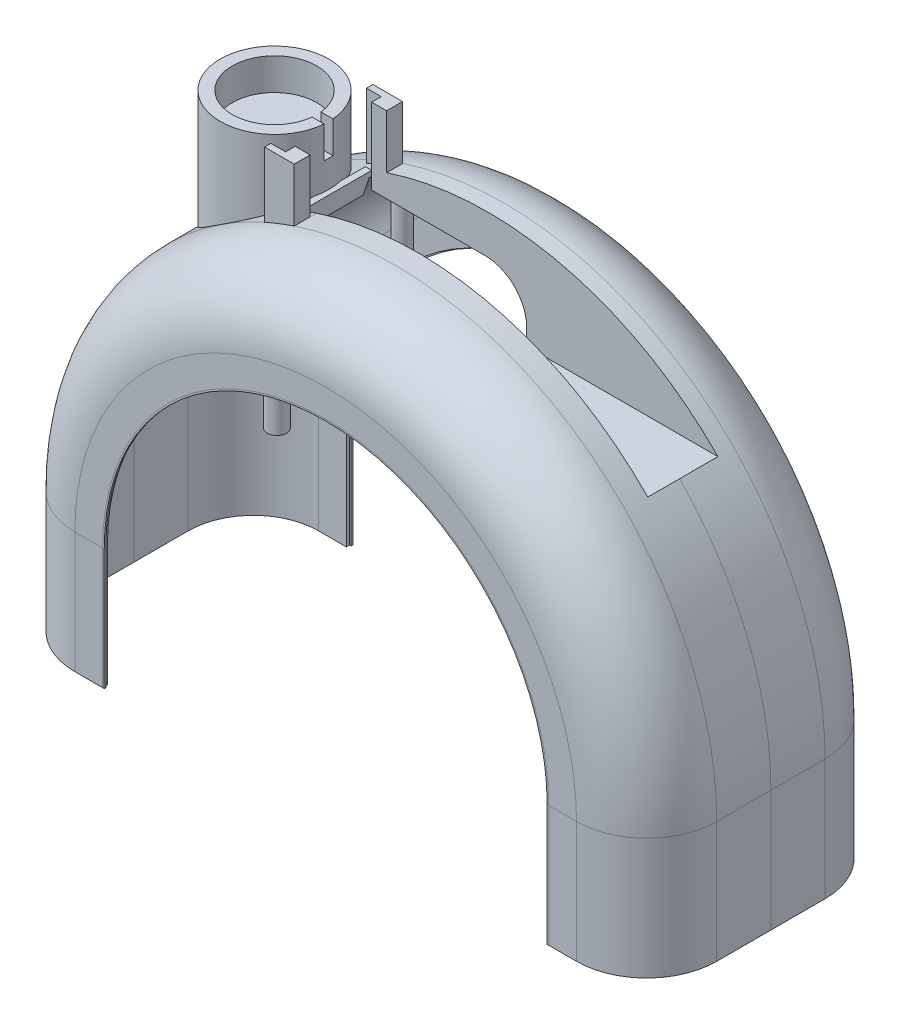
SolidWorks part; units mm, degrees
ref_plane "Front Plane" through (0, 0, 0) normal (0, 0, 1) x (1, 0, 0)
ref_plane "Top Plane" through (0, 0, 0) normal (0, 1, 0) x (1, 0, 0)
ref_plane "Right Plane" through (0, 0, 0) normal (1, 0, 0) x (0, 0, -1)
sketch "Sketch1" plane through (0, 0, 0) normal (0, 1, 0) x (1, 0, 0)
  line L0 (0, 0) -> (0, -1)
  line L1 (0, -1.5) -> (-8.7, -1.5)
  line L2 (-30.7, 20.5) -> (-30.7, 37.5)
  line L4 (0, 0) -> (-8.7, 0)
  line L5 (-29.2, 20.5) -> (-29.2, 37.5)
  line L6 (0, -1.5) -> (0.5, -1.5)
  line L7 (0.5, -1.5) -> (0.5, -1)
  line L8 (0.5, -1) -> (0, -1)
  line L9 (-64.5961, 37.5) -> (41.8012, 37.5) construction
  line L10 (0, 76.5) -> (0.5, 76.5)
  line L11 (0.5, 76.5) -> (0.5, 76)
  line L12 (0.5, 76) -> (0, 76)
  line L13 (0, 75) -> (0, 76)
  line L14 (0, 76.5) -> (-8.7, 76.5)
  line L15 (0, 75) -> (-8.7, 75)
  line L16 (-30.7, 54.5) -> (-30.7, 37.5)
  line L17 (-29.2, 54.5) -> (-29.2, 37.5)
  arc A0 (-8.7, -1.5) -> (-30.7, 20.5) centre (-8.7, 20.5) cw
  arc A1 (-8.7, 0) -> (-29.2, 20.5) centre (-8.7, 20.5) cw
  arc A2 (-8.7, 75) -> (-29.2, 54.5) centre (-8.7, 54.5) ccw
  arc A3 (-8.7, 76.5) -> (-30.7, 54.5) centre (-8.7, 54.5) ccw
  dimension "D3" = 22
  dimension "D1" = 31.2
  dimension "D2" = 39
  dimension "D5" = 0.5
  dimension "D6" = 0.5
  dimension "D4" = 1.5
sketch "Sketch3" plane through (0, 0, 0) normal (0, 0, 1) x (1, 0, 0)
  line L0 (0, 38) -> (0, 0)
  line L1 (140, 38) -> (140, 0)
  arc A0 (140, 38) -> (0, 38) centre (70, 38) ccw
  dimension "D1" = 140
  dimension "D2" = 38
sweep "Sweep1" add profiles "Sketch1" path "Sketch3"
sketch "Sketch4" plane through (0, 0, 0) normal (0, 1, 0) x (1, 0, 0)
  line L0 (148.7, 0) -> (-8.7, 0) construction
  line L1 (-29.2, 20.5) -> (-29.2, 37.5) construction
  line L2 (-106.3543, 37.5) -> (315.2775, 37.5) construction
  line L3 (0.5, -1.5) -> (139.5, -1.5) construction
  line L4 (70, -1.5) -> (70, 117.9162) construction
  circle A0 centre (-13.2, 8.6) radius 3
  circle A1 centre (153.2, 8.6) radius 3
  dimension "D1" = 6
  dimension "D2" = 8.6
  dimension "D3" = 16
extrude "Boss-Extrude7" add sketch "Sketch4" along normal up to next
ref_plane "Plane1" through (0, 0, -37.5) normal (0, 0, 1) x (1, 0, 0)
mirror "Mirror1" about plane through (0, 0, -37.5) normal (0, 0, 1) of "Boss-Extrude7"
sketch "Sketch7" plane through (0, 0, 0) normal (0, 1, 0) x (1, 0, 0)
  circle A0 centre (-13.2, 8.6) radius 3
  circle A1 centre (-13.2, 66.4) radius 3
  circle A2 centre (153.2, 8.6) radius 3
  circle A3 centre (153.2, 66.4) radius 3
extrude "Cut-Extrude2" cut sketch "Sketch7" along normal blind 35.9
ref_plane "Plane2" through (0, 108.34, 0) normal (0, -1, 0) x (-1, 0, 0)
sketch "Sketch10" plane through (0, 108.34, 0) normal (0, -1, 0) x (-1, 0, 0)
  line L0 (-142.0609, 25.5) -> (-142.0609, 49.5)
  line L1 (-142.0609, 49.5) -> (-33.4391, 49.5)
  line L2 (2.0609, 49.5) -> (2.0609, 25.5)
  line L3 (-33.4391, 25.5) -> (-142.0609, 25.5)
  line L4 (-203.39, 37.5) -> (89.1618, 37.5) construction
  line L11 (-33.4391, 25.5) -> (-33.4391, 49.5)
  point P6 (-142.0609, 37.5)
  point P12 (2.0609, 37.5)
  dimension "D1" = 24
  dimension "D2" = 35.5
extrude "Cut-Extrude4" cut sketch "Sketch10" against normal through all contours L1 L11 L3 L0
sketch "Sketch11" plane through (0, 108.34, 0) normal (0, -1, 0) x (-1, 0, 0)
  line L0 (-212.1447, 37.5) -> (55.743, 37.5) construction
  line L1 (-33.4391, 49.5) -> (-33.4391, 37.5) construction
  circle A0 centre (-14.9391, 37.5) radius 17
  dimension "D1" = 34
  dimension "D2" = 18.5
extrude "Boss-Extrude8" add sketch "Sketch11" against normal blind 42
sketch "Sketch12" plane through (0, 108.34, 0) normal (0, -1, 0) x (1, 0, 0)
  line L0 (0.0506, -29.2944) -> (0.0506, -45.7056)
  arc A0 (0.0506, -45.7056) -> (0.0506, -29.2944) centre (14.9391, -37.5) ccw
  dimension "D1" = 34
  dimension "D2" = 16.4112
extrude "Cut-Extrude5" cut sketch "Sketch12" against normal up to surface up to face at (96.3656, 108.8434, -45.1458)
sketch "Sketch13" plane through (0, 150.34, 0) normal (0, 1, 0) x (1, 0, 0)
  line L0 (-61.5448, 37.5) -> (220.1909, 37.5) construction
  line L1 (28.8102, 54.5) -> (38.1041, 54.5)
  line L2 (14.9391, 54.5) -> (170.7, 54.5) construction
  line L3 (38.1041, 54.5) -> (38.1041, 49.5)
  line L4 (33.4391, 49.5) -> (142.0609, 49.5) construction
  line L5 (38.1041, 49.5) -> (33.4391, 49.5)
  line L6 (33.4391, 49.5) -> (33.4391, 52.5)
  line L7 (33.4391, 52.5) -> (28.8102, 52.5)
  line L8 (28.8102, 52.5) -> (28.8102, 54.5)
  line L9 (33.4391, 22.5) -> (28.8102, 22.5)
  line L10 (33.4391, 25.5) -> (33.4391, 22.5)
  line L11 (38.1041, 25.5) -> (33.4391, 25.5)
  line L12 (38.1041, 20.5) -> (38.1041, 25.5)
  line L13 (28.8102, 20.5) -> (38.1041, 20.5)
  line L14 (28.8102, 22.5) -> (28.8102, 20.5)
  dimension "D1" = 9.2939
  dimension "D2" = 4.665
  dimension "D3" = 2
extrude "Boss-Extrude11" add sketch "Sketch13" against normal up to surface (20.4494 mm away) up to face at (-17.3323, 78.3149, -46.9478)
sketch "Sketch14" plane through (0, 150.34, 0) normal (0, 1, 0) x (1, 0, 0)
  line L0 (28.1165, 38.885) -> (31.8826, 38.885)
  line L1 (28.1165, 36.115) -> (31.8826, 36.115)
  arc A0 (28.1165, 38.885) -> (28.1165, 36.115) centre (14.9391, 37.5) ccw
  circle A1 centre (14.9391, 37.5) radius 17 construction
  arc A2 (14.9391, 20.5) -> (31.9391, 37.5) centre (14.9391, 37.5) ccw construction
  arc A3 (31.8826, 36.115) -> (31.8826, 38.885) centre (14.9391, 37.5) ccw
  dimension "D1" = 26.5
  dimension "D2" = 2.77
extrude "Cut-Extrude6" cut sketch "Sketch14" against normal blind 10
sketch "Sketch15" plane through (0, 108.34, 0) normal (0, -1, 0) x (-1, 0, 0)
  line L0 (-142.0609, 25.5) -> (-82.0609, 25.5)
  line L1 (-38.1041, 25.5) -> (-142.0609, 25.5) construction
  line L2 (-82.0609, 25.5) -> (-82.0609, 49.5)
  line L3 (-142.0609, 49.5) -> (-38.1041, 49.5) construction
  line L4 (-82.0609, 49.5) -> (-142.0609, 49.5)
  line L5 (-142.0609, 49.5) -> (-142.0609, 25.5)
  dimension "D1" = 60
extrude "Boss-Extrude12" add sketch "Sketch15" along normal blind 2
sketch "Sketch16" plane through (0, 0, -49.5) normal (0, 0, 1) x (1, 0, 0)
  line L0 (142.0609, 108.34) -> (82.0609, 108.34)
  line L1 (82.0609, 108.34) -> (82.0609, 137.9751)
  arc A0 (142.0609, 108.34) -> (38.1041, 133.5151) centre (70, 38) ccw construction
sketch "Sketch17" plane through (33.4391, 0, 0) normal (1, 0, 0) x (0, 0, -1)
  line L0 (25.5, 131.8285) -> (25.5, 126.4285)
  line L1 (25.5, 126.4285) -> (46.8323, 126.4285)
  line L2 (46.8323, 126.4285) -> (49.5, 131.8285)
  line L3 (49.5, 131.8285) -> (25.5, 131.8285)
  dimension "D1" = 5.4
extrude "Boss-Extrude13" add sketch "Sketch17" against normal blind 2
sketch "Sketch18" plane through (0, 0, -49.5) normal (0, 0, 1) x (1, 0, 0)
  line L0 (142.0609, 108.34) -> (141.9047, 106.34)
  line L1 (82.0609, 106.34) -> (82.0609, 113.4285)
  line L2 (82.0609, 106.34) -> (141.9047, 106.34) construction
  line L3 (33.4391, 131.8285) -> (33.4391, 130.2168) construction
  line L4 (33.4391, 126.4285) -> (69.0609, 126.4285)
  line L5 (38.1041, 133.5151) -> (33.4391, 131.8285)
  line L6 (33.4391, 126.4285) -> (33.4391, 130.2168) construction
  line L7 (33.4391, 131.8285) -> (33.4391, 130.2168)
  line L8 (33.4391, 126.4285) -> (33.4391, 130.2168)
  line L9 (82.0609, 106.34) -> (141.9047, 106.34)
  arc A0 (142.0609, 108.34) -> (38.1041, 133.5151) centre (70, 38) ccw construction
  arc A1 (142.0609, 108.34) -> (38.1041, 133.5151) centre (70, 38) ccw
  arc A2 (82.0609, 113.4285) -> (69.0609, 126.4285) centre (69.0609, 113.4285) ccw
  dimension "D1" = 13
extrude "Boss-Extrude26" add sketch "Sketch18" against normal blind 2
sketch "Sketch20" plane through (0, 0, -25.5) normal (0, 0, -1) x (-1, 0, 0)
  line L0 (-141.9047, 106.34) -> (-82.0609, 106.34)
  line L1 (-82.0609, 106.34) -> (-82.0609, 113.4285)
  line L2 (-33.4391, 131.8285) -> (-33.4391, 130.2168) construction
  line L3 (-33.4391, 130.2168) -> (-33.4391, 126.4285) construction
  line L4 (-33.4391, 131.8285) -> (-33.4391, 130.2168)
  line L5 (-33.4391, 130.2168) -> (-33.4391, 126.4285)
  line L6 (-33.4391, 126.4285) -> (-69.0609, 126.4285)
  line L7 (-33.4391, 131.8285) -> (-38.1041, 133.5151)
  line L8 (-142.0609, 108.34) -> (-141.9047, 106.34)
  arc A1 (-38.1041, 133.5151) -> (-142.0609, 108.34) centre (-70, 38) ccw construction
  arc A2 (-38.1041, 133.5151) -> (-142.0609, 108.34) centre (-70, 38) ccw
  arc A3 (-82.0609, 113.4285) -> (-69.0609, 126.4285) centre (-69.0609, 113.4285) cw
  dimension "D1" = 13
extrude "Boss-Extrude28" add sketch "Sketch20" along normal blind 2
sketch "Sketch22" plane through (0, 0, 0) normal (0, -1, 0) x (1, 0, 0)
  line L0 (170.7, -54.5) -> (170.7, -37.5) construction
  line L1 (0, -76.5) -> (-8.7, -76.5) construction
  line L2 (-8.7, 1.5) -> (0, 1.5) construction
  circle A0 centre (30.25, -62.3) radius 2.5
  circle A1 centre (30.25, -16.7) radius 2.5
  circle A2 centre (86.32, -16.7) radius 2.5
  circle A3 centre (86.32, -66.3) radius 2.5
  dimension "D1" = 84.38
  dimension "D3" = 140.45
  dimension "D4" = 18.2
  dimension "D5" = 5
  dimension "D6" = 5
  dimension "D7" = 5
  dimension "D8" = 5
  dimension "D9" = 14.2
  dimension "D2" = 10.2
extrude "Boss-Extrude29" add sketch "Sketch22" against normal up to next
sketch "Sketch24" plane through (0, 0, 0) normal (0, -1, 0) x (1, 0, 0)
  circle A0 centre (30.25, -16.7) radius 2.5
  circle A1 centre (30.25, -62.3) radius 2.5
extrude "Cut-Extrude8" cut sketch "Sketch24" against normal blind 98.5
sketch "Sketch25" plane through (0, 0, 0) normal (0, -1, 0) x (1, 0, 0)
  circle A0 centre (86.32, -16.7) radius 2.5
  circle A1 centre (86.32, -66.3) radius 2.5
extrude "Cut-Extrude9" cut sketch "Sketch25" against normal blind 108
sketch "Sketch28" plane through (0, 98.5, 0) normal (0, -1, 0) x (-1, 0, 0)
  point P0 (-86.32, 66.3)
  point P3 (-30.25, 62.3)
  point P6 (-86.32, 16.7)
  point P9 (-30.25, 16.7)
  point P12 (13.2, 8.6)
  point P15 (13.2, 66.4)
  point P18 (-153.2, 66.4)
  point P21 (-153.2, 8.6)
sketch "Sketch45" plane through (0, 108, 0) normal (0, -1, 0) x (-1, 0, 0)
  point P0 (-86.32, 66.3)
sketch "Sketch46" plane through (0, 35.9, 0) normal (0, -1, 0) x (1, 0, 0)
  circle A0 centre (-13.2, -66.4) radius 1.25
  circle A1 centre (-13.2, -8.6) radius 1.25
  circle A2 centre (153.2, -8.6) radius 1.25
  circle A3 centre (153.2, -66.4) radius 1.25
  dimension "D1" = 2.5
  dimension "D2" = 2.5
  dimension "D3" = 2.5
  dimension "D4" = 2.5
extrude "Cut-Extrude10" cut sketch "Sketch46" against normal blind 10
sketch "Sketch47" plane through (0, 108, 0) normal (0, -1, 0) x (1, 0, 0)
  circle A0 centre (86.32, -66.3) radius 1.25
  circle A1 centre (86.32, -16.7) radius 1.25
  dimension "D1" = 2.5
  dimension "D2" = 2.5
extrude "Cut-Extrude11" cut sketch "Sketch47" against normal blind 10
sketch "Sketch48" plane through (0, 98.5, 0) normal (0, -1, 0) x (1, 0, 0)
  circle A0 centre (30.25, -16.7) radius 1.25
  circle A1 centre (30.25, -62.3) radius 1.25
  dimension "D1" = 2.5
  dimension "D2" = 2.5
extrude "Cut-Extrude12" cut sketch "Sketch48" against normal blind 10
sketch "Sketch49" plane through (0, 35.9, 0) normal (0, -1, 0) x (1, 0, 0)
  circle A0 centre (-13.2, -8.6) radius 3 construction
  circle A1 centre (153.2, -66.4) radius 3
  circle A2 centre (153.2, -66.4) radius 3
  circle A3 centre (-13.2, -8.6) radius 3
  circle A4 centre (153.2, -8.6) radius 1.25 construction
  circle A5 centre (153.2, -8.6) radius 3 construction
  circle A6 centre (-13.2, -66.4) radius 3 construction
  circle A7 centre (-13.2, -66.4) radius 1.25 construction
  circle A8 centre (153.2, -8.6) radius 1.25
  circle A9 centre (153.2, -8.6) radius 3
  circle A10 centre (-13.2, -66.4) radius 3
  circle A11 centre (-13.2, -66.4) radius 1.25
  circle A12 centre (153.2, -66.4) radius 1.25 construction
  circle A13 centre (153.2, -66.4) radius 1.25
  dimension "D1" = 0
extrude "Boss-Extrude30" add sketch "Sketch49" along normal blind 5.8
